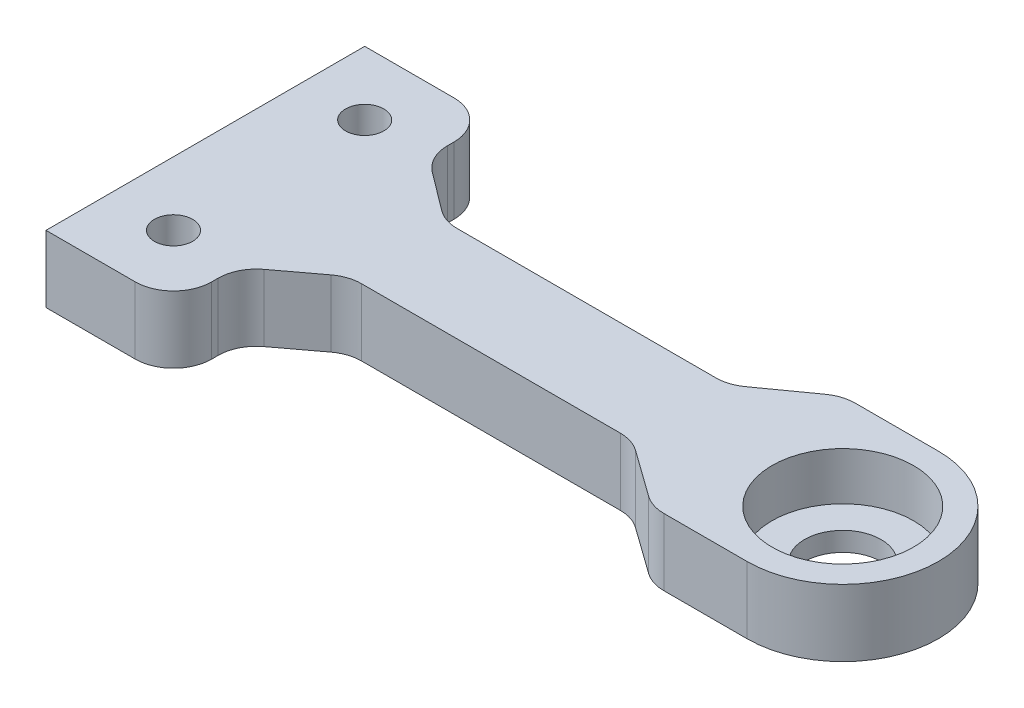
SolidWorks part; units mm, degrees
ref_plane "Front Plane" through (0, 0, 0) normal (0, 0, 1) x (1, 0, 0)
ref_plane "Top Plane" through (0, 0, 0) normal (0, 1, 0) x (1, 0, 0)
ref_plane "Right Plane" through (0, 0, 0) normal (1, 0, 0) x (0, 0, -1)
sketch "Sketch1" plane through (0, 0, 0) normal (0, 1, 0) x (1, 0, 0)
  line L1 (-57.5, -15) -> (57.5, -15)
  line L2 (-57.5, -15) -> (-57.5, 15)
  line L3 (-57.5, 15) -> (57.5, 15)
  line L4 (57.5, -15) -> (57.5, 15)
  line L5 (-57.5, -15) -> (57.5, 15) construction
  line L6 (-57.5, 15) -> (57.5, -15) construction
  point P0 (0, 0)
  dimension "D1" = 115
  dimension "D2" = 30
extrude "Boss-Extrude1" add sketch "Sketch1" along normal blind 10.5
sketch "Sketch2" plane through (0, 0, 0) normal (0, 1, 0) x (1, 0, 0)
  line L0 (-57.5, 15) -> (-57.5, -15) construction
  circle A0 centre (42.5, 0) radius 11.1
  dimension "D1" = 22.2
  dimension "D2" = 100
extrude "Cut-Extrude1" cut sketch "Sketch2" along normal blind 10.5 from offset 3
sketch "Sketch3" plane through (0, 0, 0) normal (0, 1, 0) x (1, 0, 0)
  circle A0 centre (42.5, 0) radius 6
  dimension "D1" = 12
extrude "Cut-Extrude4" cut sketch "Sketch3" along normal blind 10.5
sketch "Sketch5" plane through (0, 0, 0) normal (0, 1, 0) x (1, 0, 0)
  line L0 (-57.5, 15) -> (-57.5, 25)
  line L1 (-57.5, 25) -> (-37.5, 25)
  line L2 (-37.5, 25) -> (-37.5, -25)
  line L3 (-37.5, -25) -> (-57.5, -25)
  line L5 (-57.5, -25) -> (-57.5, -15)
  line L6 (-57.5, -15) -> (-57.5, 15)
  dimension "D1" = 20
  dimension "D2" = 10
extrude "Boss-Extrude2" add sketch "Sketch5" along normal blind 10.5
sketch "Sketch6" plane through (0, 10.5, 0) normal (0, 1, 0) x (1, 0, 0)
  line L0 (-37.5, 15) -> (-57.5, 15) construction
  line L1 (-57.5, 25) -> (-57.5, -25) construction
  line L2 (-37.5, -15) -> (-57.5, -15) construction
  circle A0 centre (-47.5, -15) radius 2.25
  circle A1 centre (-47.5, 15) radius 2.25
  dimension "D1" = 4.5
extrude "Cut-Extrude5" cut sketch "Sketch6" against normal blind 10.5
sketch "Sketch7" plane through (0, 10.5, 0) normal (0, 1, 0) x (1, 0, 0)
  circle A0 centre (-47.5, 15) radius 3
  circle A1 centre (-47.5, -15) radius 3
  dimension "D1" = 6
extrude "Cut-Extrude6" cut sketch "Sketch7" against normal blind 7.5
sketch "Sketch8" plane through (0, 10.5, 0) normal (0, 1, 0) x (1, 0, 0)
  line L0 (-57.5, 0) -> (57.5, 0) construction
  line L1 (-57.5, 25) -> (-57.5, -25) construction
  line L2 (57.5, -15) -> (57.5, 15) construction
  line L3 (-37.5, 15) -> (-27.5, 7.5)
  line L4 (-27.5, 7.5) -> (17.0229, 7.5)
  line L5 (17.0229, 7.5) -> (27.5, 15)
  line L6 (57.5, 15) -> (-37.5, 15) construction
  line L7 (-37.5, 15) -> (27.5, 15)
  line L8 (-37.5, -15) -> (27.5, -15)
  line L9 (17.0229, -7.5) -> (27.5, -15)
  line L10 (-27.5, -7.5) -> (17.0229, -7.5)
  line L11 (-37.5, -15) -> (-27.5, -7.5)
  circle A0 centre (42.5, 0) radius 6 construction
  point P19 (-28.7656, 7.5)
  dimension "D1" = 15
  dimension "D2" = 15
  dimension "D3" = 10
extrude "Cut-Extrude7" cut sketch "Sketch8" against normal blind 28.5
fillet "Fillet1" radius 6 10 edges at (27.5, 5.25, 15) (17.0229, 5.25, 7.5) (27.5, 5.25, -15) (17.0229, 5.25, -7.5) (-37.5, 5.25, 25) (-37.5, 5.25, 15) (-27.5, 5.25, 7.5) (-37.5, 5.25, -25) (-37.5, 5.25, -15) (-27.5, 5.25, -7.5)
fillet "Fillet2" 2 edges at (57.5, 5.25, -15) (57.5, 5.25, 15) type full round first side face at (43.4631, 5.25, -15) second side face at (43.4631, 5.25, 15) middle face at (57.5, 5.25, 0)
